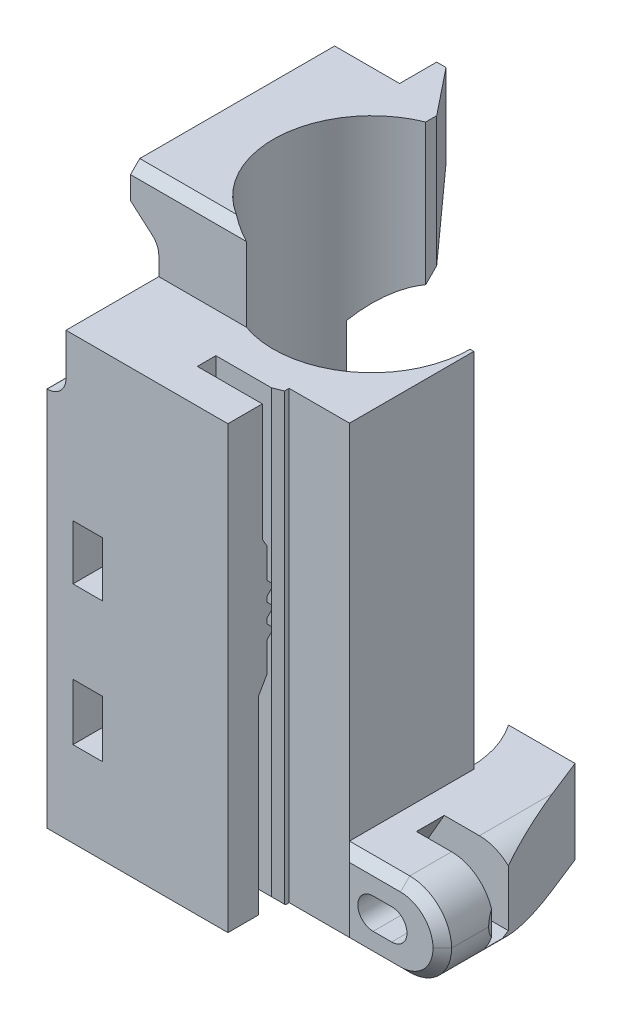
SolidWorks part; units mm, degrees
material "Custom Plastic"
ref_plane "Front Plane" through (0, 0, 0) normal (0, 0, 1) x (1, 0, 0)
ref_plane "Top Plane" through (0, 0, 0) normal (0, 1, 0) x (1, 0, 0)
ref_plane "Right Plane" through (0, 0, 0) normal (1, 0, 0) x (0, 0, -1)
sketch "Sketch2" plane through (0, 0, 0) normal (0, 1, 0) x (1, 0, 0)
  line L0 (22, -14.4) -> (22, -9.4)
  line L1 (16, 6) -> (16, -12.9) construction
  line L2 (11, -13.4) -> (4.5, -13.4)
  line L3 (4.5, -13.4) -> (4.5, -20)
  line L4 (4.5, -20) -> (-15, -20)
  line L5 (-15, -20) -> (-15, 16)
  line L6 (22, -9.4) -> (14.1647, -9.4) construction
  line L7 (8.7384, 6) -> (15.906, 6)
  line L8 (-15, 16) -> (-4, 16)
  line L9 (-4, 16) -> (-4, 9.8163)
  line L10 (11, -13.4) -> (12, -14.4)
  line L11 (12, -14.4) -> (22, -14.4)
  line L12 (22, -9.4) -> (15.906, 6)
  circle A0 centre (0, 0) radius 10.5 construction
  arc A1 (-4, 9.8163) -> (8.7384, 6) centre (0, 0) ccw
  arc A3 (14.1647, -9.4) -> (15.906, 6) centre (0, 0) ccw construction
  dimension "D1" = 21
  dimension "D2" = 0.1
  dimension "D11" = 17
  dimension "D3" = 4.5
  dimension "D4" = 16
  dimension "D5" = 15
  dimension "D6" = 13.4
  dimension "D7" = 20
  dimension "D8" = 16
  dimension "D9" = 4
  dimension "D10" = 6
  dimension "D12" = 22
  dimension "D14" = 45
  dimension "D15" = 11
  dimension "D16" = 1
extrude "Boss-Extrude1" add sketch "Sketch2" along normal blind 37 and the other way blind 20
sketch "Sketch3" plane through (0, 0, 0) normal (0, -1, 0) x (1, 0, 0)
  circle A0 centre (0, 0) radius 10.5
  dimension "D1" = 21
extrude "Cut-Extrude1" [suppressed] cut sketch "Sketch3" against normal blind 20 from offset 4 offset against normal yes
mirror "Mirror1" [suppressed] about plane through (0, 0, 0) normal (0, 1, 0)
sketch "Sketch4" plane through (0, 37, 0) normal (0, -1, 0) x (1, 0, 0)
  line L0 (4.5, 20) -> (4.5, 13.4) construction
  line L1 (-15, 20) -> (4.5, 20)
  line L2 (-15, 20) -> (-15, 9.9962)
  line L3 (-15, 9.9962) -> (4.5, 9.9962)
  line L4 (4.5, 20) -> (4.5, 9.9962)
extrude "Cut-Extrude3" [suppressed] cut sketch "Sketch4" along normal blind 11
sketch "Sketch5" plane through (4.5, 0, 0) normal (1, 0, 0) x (0, 0, -1)
  line L0 (-15.8, 5.718) -> (-15.3, 6.218)
  line L1 (-14.3, -20) -> (-16.3, -20)
  line L2 (-14.3, -20) -> (-14.3, 37)
  line L3 (-16.3, 37) -> (-14.3, 37)
  line L4 (-15.8, 2.5) -> (-15.8, 5.718)
  line L5 (-15.3, 6.218) -> (-15.3, 6.718)
  line L6 (-15.3, 6.718) -> (-15.8, 7.218)
  line L7 (-15.8, 9.782) -> (-15.3, 10.282)
  line L8 (-15.3, 10.282) -> (-15.3, 10.782)
  line L9 (-15.3, 10.782) -> (-15.8, 11.282)
  line L10 (-15.8, 7.75) -> (-15.3, 8.25)
  line L11 (-15.3, 8.25) -> (-15.3, 8.75)
  line L12 (-15.3, 8.75) -> (-15.8, 9.25)
  line L13 (-15.8, 9.25) -> (-15.8, 9.782)
  line L14 (-15.8, 2.5) -> (-16.3, 1.634)
  line L15 (-15.8, 7.218) -> (-15.8, 7.75)
  line L16 (-16.3, 1.634) -> (-16.3, -20)
  line L17 (-15.8, 11.282) -> (-15.8, 14.5)
  line L18 (-15.8, 14.5) -> (-16.3, 15.366)
  line L19 (-20, -20) -> (-13.4, -20) construction
  line L20 (16, 8.5) -> (-15.3, 8.5) construction
  line L21 (-16.3, 15.366) -> (-16.3, 37)
  line L22 (-20, 37) -> (-13.4, 37) construction
  line L23 (16, -20) -> (16, 37) construction
  dimension "D1" = 0.5
  dimension "D2" = 0.5
  dimension "D3" = 2.032
  dimension "D4" = 1.5
  dimension "D5" = 2
  dimension "D6" = 14.3
  dimension "D7" = 6
  dimension "D8" = 150
extrude "Cut-Extrude5" cut sketch "Sketch5" against normal blind 7
chamfer "Chamfer1" [suppressed] distance 1.2 angle 45
chamfer "Chamfer3" distance 0.5 angle 45 9 edges at (1, -20, 14.3) (-3.0421, -20, 10.1541) (-4, -20, -12.9082) (-9.5, -20, -16) (-15, -20, 2) (-5.25, -20, 20) (4.5, -20, 18.15) (1, -20, 16.3) (-2.5, -20, 15.3)
sketch "Sketch6" plane through (-15, 0, 0) normal (-1, 0, 0) x (0, 0, 1)
  line L0 (13, 7.5) -> (13, -7.5) construction
  line L1 (0, 0) -> (13, 0) construction
  circle A0 centre (13, 7.5) radius 1.55
  circle A1 centre (13, -7.5) radius 1.55
  dimension "D2" = 3.1
  dimension "D1" = 15
  dimension "D3" = 13
extrude "Cut-Extrude6" cut sketch "Sketch6" against normal blind 10
sketch "Sketch7" plane through (-15, 0, 0) normal (-1, 0, 0) x (0, 0, 1)
  line L0 (21.3141, -4.2) -> (21.3141, -10.3)
  line L1 (9.3668, -7.5) -> (10.9834, -10.3)
  line L2 (10.9834, -10.3) -> (21.3141, -10.3)
  line L3 (11.3834, 4.7) -> (9.7668, 7.5)
  line L4 (21.3141, 4.7) -> (11.3834, 4.7)
  line L5 (21.3141, -4.7) -> (11.3834, -4.7) construction
  line L6 (11.2721, -4.2) -> (9.3668, -7.5)
  line L7 (-3, 8.5) -> (19.4531, 8.5) construction
  line L8 (11.2721, -4.2) -> (21.3141, -4.2)
  line L9 (11.3834, 10.3) -> (21.7141, 10.3) construction
  line L10 (13.1374, -12.1691) -> (15.0359, -8.8809) construction
  line L11 (16.6078, -8.8418) -> (15.5516, -7.0123) construction
  line L12 (9.7668, 7.5) -> (11.5566, 10.6)
  line L13 (21.3141, 4.7) -> (21.3141, 10.6)
  line L14 (11.5566, 10.6) -> (21.3141, 10.6)
  circle A0 centre (12.6, -7.5) radius 2.8 construction
  circle A2 centre (13, 7.5) radius 2.8 construction
  circle A3 centre (13, 7.5) radius 1.55 construction
  point P4 (13, -7.5)
  dimension "D1" = 5.6
  dimension "D2" = 0.4
  dimension "D3" = 0.5
  dimension "D4" = 0.3
extrude "Cut-Extrude7" cut sketch "Sketch7" against normal blind 3.2 from offset 2.8 offset against normal yes
sketch "Sketch9" plane through (-15, 0, 0) normal (-1, 0, 0) x (0, 0, 1)
  line L0 (-16, 28) -> (-6, 18)
  line L1 (-16, -19.5) -> (-16, 37) construction
  line L2 (-6, 18) -> (-6, -20)
  line L3 (-16, -20) -> (20, -20) construction
  line L4 (-6, -20) -> (-16, -20)
  line L5 (-16, -20) -> (-16, 28)
  line L6 (-16, 37) -> (20, 37) construction
  dimension "D1" = 9
  dimension "D2" = 6
  dimension "D3" = 45
extrude "Cut-Extrude9" cut sketch "Sketch9" against normal blind 12 and the other way blind 10
sketch "Sketch12" plane through (-15, 0, 0) normal (-1, 0, 0) x (0, 0, 1)
  line L0 (8, 37) -> (8, 30)
  line L1 (-16, 37) -> (20, 37) construction
  line L2 (5, 25) -> (-13, 25)
  line L3 (-16, 28) -> (-13, 25)
  line L4 (-16, 28) -> (-6, 18) construction
  line L5 (-16, 28) -> (-16, 37)
  line L6 (-16, 37) -> (8, 37)
  line L7 (8, 30) -> (5, 30)
  line L8 (5, 30) -> (5, 25)
  dimension "D1" = 24
  dimension "D2" = 12
  dimension "D3" = 3
  dimension "D4" = 5
extrude "Boss-Extrude2" add sketch "Sketch12" along normal blind 1
sketch "Sketch10" plane through (0, 0, -16) normal (0, 0, -1) x (-1, 0, 0)
  line L1 (16, 37) -> (9, 37)
  line L2 (16, 37) -> (16, 28.8)
  line L3 (16, 28.8) -> (9, 28.8)
  line L4 (9, 37) -> (9, 28.8)
  line L5 (16, 37) -> (16, 28) construction
  line L6 (4, 28) -> (16, 28) construction
  line L7 (4, 37) -> (16, 37) construction
  dimension "D1" = 7
  dimension "D3" = 0.8
extrude "Cut-Extrude10" cut sketch "Sketch10" against normal blind 4
sketch "Sketch11" plane through (-16, 0, 0) normal (-1, 0, 0) x (0, 0, 1)
  line L0 (-12, 28.8) -> (-16, 28.8) construction
  line L2 (-16, 28) -> (-16, 28.8) construction
  circle A0 centre (-9, 26.3) radius 1.25
  circle A1 centre (1, 26.3) radius 1.25
  dimension "D3" = 10
  dimension "D4" = 2.5
  dimension "D1" = 2.5
  dimension "D2" = 7
extrude "Cut-Extrude11" cut sketch "Sketch11" against normal blind 4
chamfer "Chamfer4" distance 3 angle 45 2 edges
sketch "Sketch13" plane through (0, 37, 0) normal (0, 1, 0) x (1, 0, 0)
  line L0 (-16, -10) -> (0, -10)
  line L1 (0, -10) -> (0, 6.4112)
  line L2 (-16, -10) -> (-16, -20)
  line L3 (12, -20) -> (-16, -20)
  line L4 (0, 6.4112) -> (12, 6.4112)
  line L5 (12, -20) -> (12, 6.4112)
  line L7 (-15, -20) -> (4.5, -20) construction
extrude "Cut-Extrude12" cut sketch "Sketch13" against normal blind 9
chamfer "Chamfer5" distance 1 angle 45 1 edges at (-9.7578, 37, 10)
sketch "Sketch15" plane through (0, -20, -7.1) normal (0, 1, 0) x (1, 0, 0)
  line L1 (22, -21.5) -> (11, -21.5)
  line L2 (22, -21.5) -> (22, -1.1)
  line L3 (22, -1.1) -> (8.1933, -1.1)
  line L4 (11, -21.5) -> (11, -7.1)
  line L5 (11, -7.1) -> (8.1933, -7.1)
  line L6 (8.1933, -7.1) -> (8.1933, -1.1)
  dimension "D1" = 11
extrude "Cut-Extrude14" cut sketch "Sketch15" along normal through all from offset 9
chamfer "Chamfer6" distance 1 angle 45 1 edges at (-15, -0.75, -6)
chamfer "Chamfer7" distance 0.4 distance2 1 1 edges at (4.5, 4.25, 14.3) first distance on face at (4.5, -0.7, 13.84)
chamfer "Chamfer10" distance 0.4 distance2 2 1 edges at (4.5, -8.933, 16.3) first distance on face at (4.5, 7.65, 16.17)
sketch "Sketch17" plane through (0, 0, 14.4) normal (0, 0, 1) x (1, 0, 0)
  line L0 (15.55, -15.5) -> (22, -15.5) construction
  line L1 (22, -20) -> (22, -11) construction
  line L2 (14.55, -15.5) -> (16.55, -15.5) construction
  line L3 (14.55, -13.85) -> (16.55, -13.85)
  line L4 (14.55, -17.15) -> (16.55, -17.15)
  circle A0 centre (15.55, -15.5) radius 4.5 construction
  arc A1 (14.55, -13.85) -> (14.55, -17.15) centre (14.55, -15.5) ccw
  arc A2 (16.55, -17.15) -> (16.55, -13.85) centre (16.55, -15.5) ccw
  point P2 (11.05, -15.5)
  point P9 (15.55, -15.5)
  dimension "D2" = 9
  dimension "D3" = 1.65
  dimension "D1" = 11.05
  dimension "D4" = 2
extrude "Cut-Extrude16" cut sketch "Sketch17" against normal blind 6
fillet "Fillet2" radius 4.5 2 edges at (22, -11, 11.9) (22, -20, 11.9)
sketch "Sketch18" plane through (0, 0, 14.4) normal (0, 0, -1) x (-1, 0, 0)
  line L0 (-22.7084, -8.1113) -> (-22.7084, -18.3)
  line L1 (-11.1168, -15.5) -> (-15.3827, -8.1113)
  line L3 (-22.7084, -8.1113) -> (-15.3827, -8.1113)
  line L5 (-22.7084, -18.3) -> (-12.7334, -18.3)
  line L6 (-12.7334, -18.3) -> (-11.1168, -15.5)
  line L9 (-16.6786, -13.9332) -> (-17.4868, -15.3332) construction
  line L10 (-17.5832, -15.5) -> (-15.6036, -18.9286) construction
  line L11 (-12.7334, -12.7) -> (-14.35, -12.7) [skipped]
  circle A0 centre (-14.35, -15.5) radius 2.8 construction
  arc A3 (-14.55, -17.15) -> (-14.55, -13.85) centre (-14.55, -15.5) ccw construction
  point P10 (-14.55, -15.5)
  dimension "D2" = 5.6
  dimension "D1" = 0.2
extrude "Cut-Extrude17" cut sketch "Sketch18" against normal blind 0.5 and the other way blind 2.5 from offset 6
chamfer "Chamfer14" distance 1 angle 45 4 edges at (14.75, -11, 14.4) (20.682, -12.318, 14.4) (20.682, -18.682, 14.4) (14.75, -20, 14.4)
sketch "Sketch19" plane through (0, 0, 20) normal (0, 0, 1) x (1, 0, 0)
  line L1 (-12.95, 30) -> (-12.95, 23.5001)
  line L2 (-14.95, 21.5001) -> (-16, 21.5001)
  line L6 (-15, 28) -> (4.5, 28) construction
  line L8 (-16, 33.5678) -> (-16, 21.5001)
  line L10 (-15, -19.5) -> (-15, 28) construction
  line L12 (-16, 33.5678) -> (-13.6361, 31.5078)
  line L13 (-16, 30) -> (-16, 36) construction
  arc A0 (-12.95, 30) -> (-13.6361, 31.5078) centre (-14.95, 30) ccw
  arc A1 (-14.95, 21.5001) -> (-12.95, 23.5001) centre (-14.95, 23.5001) ccw
  dimension "D1" = 4
  dimension "D2" = 2.05
  dimension "D3" = 2
extrude "Cut-Extrude18" cut sketch "Sketch19" against normal blind 15
chamfer "Chamfer15" distance 4 distance2 5 1 edges at (-4, 32.5, -16) first distance on face at (-9.6667, 31.2667, -16)
equation "\"y-plate-thickness\"=5"
equation "\"bed-plate-thickness\"=3"
equation "\"x-plate-thickness\"=5"
equation "\"rod-diameter\"=12"
equation "\"D1@Sketch15\"=\"rod-diameter\"/2+\"x-plate-thickness\""
